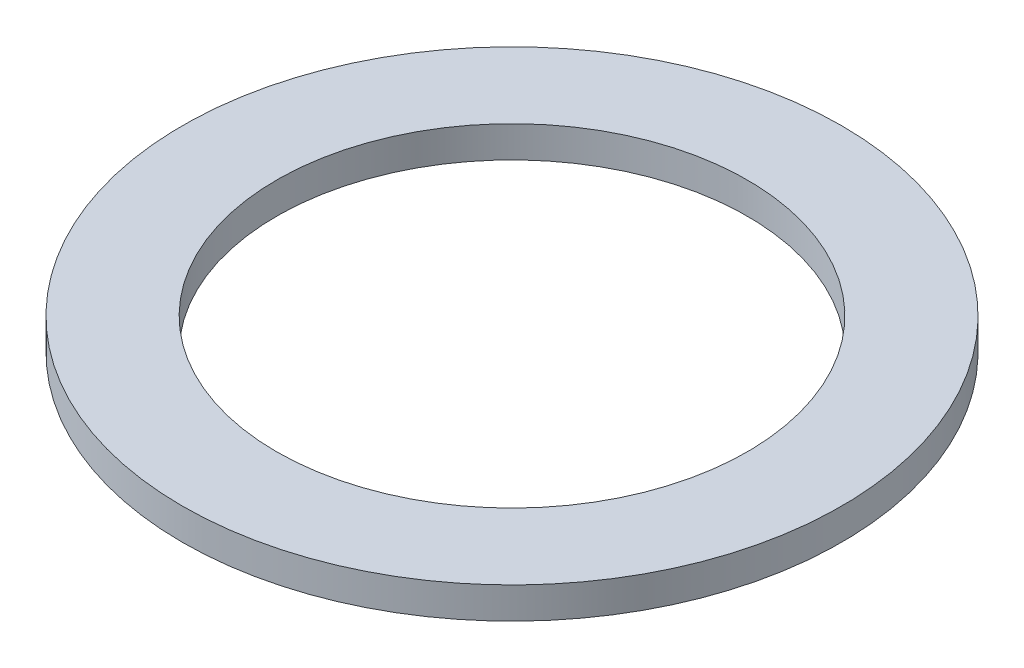
SolidWorks part; units mm, degrees
ref_plane "Front Plane" through (0, 0, 0) normal (0, 0, 1) x (1, 0, 0)
ref_plane "Top Plane" through (0, 0, 0) normal (0, 1, 0) x (1, 0, 0)
ref_plane "Right Plane" through (0, 0, 0) normal (1, 0, 0) x (0, 0, -1)
sketch "Sketch1" plane through (0, 0, 0) normal (0, 1, 0) x (1, 0, 0)
  circle A0 centre (0, 0) radius 52.5
  dimension "FLANGE_OD" = 105
extrude "Boss-Extrude1" add sketch "Sketch1" along normal blind 5
sketch "Sketch2" plane through (0, 0, 0) normal (0, 1, 0) x (1, 0, 0)
  circle A0 centre (0, 0) radius 37.5
  dimension "BORE_D" = 75
extrude "Cut-Extrude1" cut sketch "Sketch2" along normal through all
sketch "Sketch3" plane through (0, 5, 0) normal (0, 1, 0) x (1, 0, 0)
  circle A0 centre (0, 0) radius 22.3169 construction
  circle A1 centre (-22.3169, 0) radius 2.2199
  dimension "BOLT_D" = 4.4397
  dimension "BOLT_PCD" = 44.6339
extrude "Cut-Extrude2" cut sketch "Sketch3" against normal blind 4.0269 rebuild error yes
pattern_circular "CirPattern1" count 4 over 360 rebuild error yes
